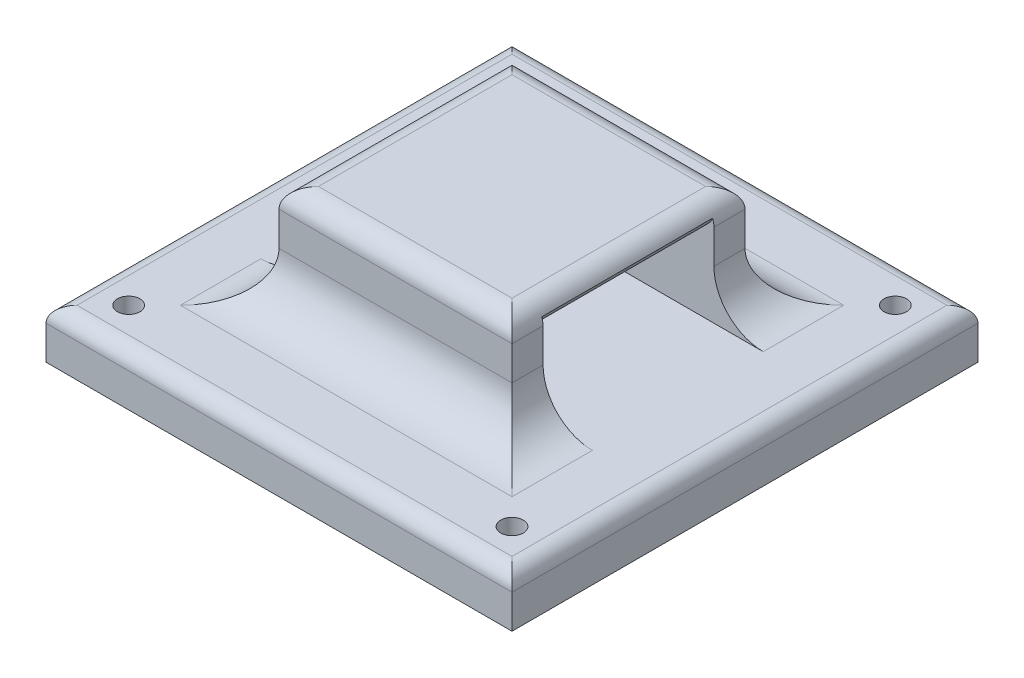
SolidWorks part; units mm, degrees
material "ABS"
ref_plane "Front Plane" through (0, 0, 0) normal (0, 0, 1) x (1, 0, 0)
ref_plane "Top Plane" through (0, 0, 0) normal (0, 1, 0) x (1, 0, 0)
ref_plane "Right Plane" through (0, 0, 0) normal (1, 0, 0) x (0, 0, -1)
sketch "Sketch2" plane through (0, 0, 0) normal (1, 0, 0) x (0, 0, -1)
  line L0 (0, -11.35) -> (0, 0) construction
  line L1 (-11, -5) -> (11, -5)
  line L2 (-11, -5) -> (-11, 5)
  line L3 (-11, 5) -> (11, 5)
  line L4 (11, -5) -> (11, 5)
  line L5 (-11, -5) -> (11, 5) construction
  line L6 (-11, 5) -> (11, -5) construction
  line L7 (-15, -11.35) -> (15, -11.35)
  line L8 (-15, -11.35) -> (-15, 8.25)
  line L9 (-15, 8.25) -> (15, 8.25)
  line L10 (15, -11.35) -> (15, 8.25)
  point P0 (0, 0)
  point P5 (0, 0)
  dimension "D1" = 22
  dimension "D2" = 30
  dimension "D3" = 3.25
  dimension "D4" = 10
  dimension "D5" = 6.35
extrude "Boss-Extrude2" add sketch "Sketch2" along normal mid plane 30
sketch "Sketch3" plane through (0, -11.35, 0) normal (0, -1, 0) x (1, 0, 0)
  line L0 (15, 15) -> (-15, 15) construction
  line L1 (-30, -30) -> (30, -30)
  line L2 (-30, -30) -> (-30, 30)
  line L3 (-30, 30) -> (30, 30)
  line L4 (30, -30) -> (30, 30)
  line L5 (15, -15) -> (-15, -15) construction
  line L6 (-15, 15) -> (-15, -15) construction
  line L7 (15, 15) -> (15, -15) construction
  dimension "D1" = 15
  dimension "D2" = 15
  dimension "D3" = 15
  dimension "D4" = 15
extrude "Boss-Extrude3" add sketch "Sketch3" against normal up to surface (6.35 mm away) up to face at (0, -5, 0)
fillet "Fillet1" radius 6.35 6 edges at (15, -5, -13) (15, -5, 13) (-15, -5, 13) (-15, -5, -13) (0, -5, -15) (0, -5, 15)
fillet "Fillet2" radius 2.54 4 edges at (15, 8.25, 0) (0, 8.25, -15) (-15, 8.25, 0) (0, 8.25, 15)
fillet "Fillet3" radius 2.54 2 edges at (-15, 5, 0) (15, 5, 0)
fillet "Fillet4" radius 2 4 edges at (30, -5, 0) (0, -5, 30) (-30, -5, 0) (0, -5, -30)
sketch "Sketch4" plane through (0, -5, 0) normal (0, 1, 0) x (1, 0, 0)
  line L0 (-21.35, 21.35) -> (-28, 28) construction
  line L1 (0, -55) -> (0, 55) construction
  line L2 (-55, 0) -> (55, 0) construction
  circle A0 centre (-24.675, 24.675) radius 1.45
  circle A1 centre (24.675, 24.675) radius 1.45
  circle A2 centre (24.675, -24.675) radius 1.45
  circle A3 centre (-24.675, -24.675) radius 1.45
  dimension "D1" = 2.9
extrude "Cut-Extrude1" cut sketch "Sketch4" against normal through all
